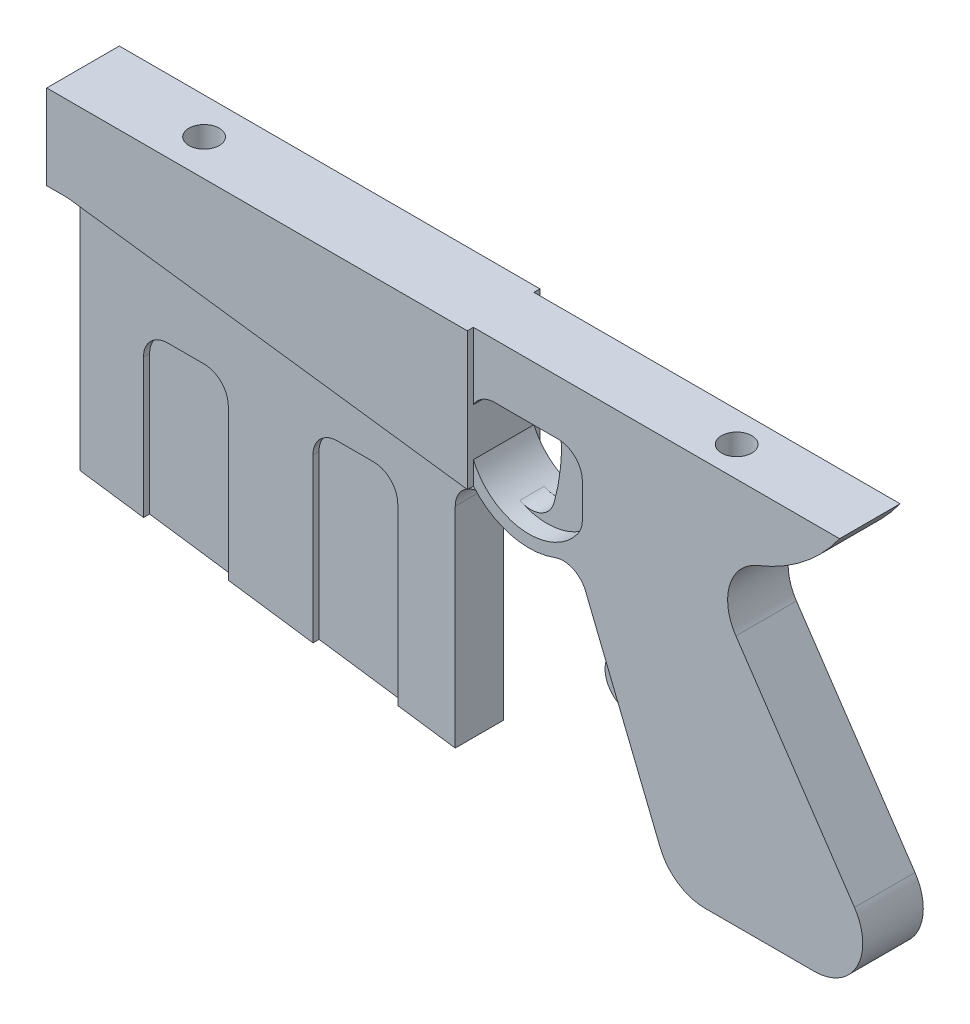
SolidWorks part; units mm, degrees
ref_plane "前视基准面" through (0, 0, 0) normal (0, 0, 1) x (1, 0, 0)
ref_plane "上视基准面" through (0, 0, 0) normal (0, 1, 0) x (1, 0, 0)
ref_plane "右视基准面" through (0, 0, 0) normal (1, 0, 0) x (0, 0, -1)
sketch "草图1" plane through (0, 0, 0) normal (0, 0, 1) x (1, 0, 0)
  line L0 (0, 0) -> (130, 0)
  line L1 (0, 0) -> (0, -14)
  line L2 (0, -14) -> (3.5, -14)
  line L3 (3.5, -14) -> (65.5, -22.7135)
  line L4 (65.5, -22.7135) -> (69.5, -22.7135)
  line L5 (88.0267, -28.48) -> (100.3562, -58.9969)
  line L6 (107.7737, -64) -> (125.8318, -64)
  line L7 (112.8677, -22.4735) -> (132.4641, -51.5265)
  line L8 (100.3562, -58.9969) -> (110.2182, -83.4061) construction
  line L9 (107.7737, -64) -> (101.1244, -64) construction
  line L10 (132.4641, -51.5265) -> (151.8382, -80.2497) construction
  line L11 (125.8318, -64) -> (183.2741, -64) construction
  line L13 (83.5, -9) -> (73, -9)
  line L14 (69, -13) -> (69, -17.4609)
  line L15 (3.5, -14) -> (3.5, -54)
  line L16 (3.5, -54) -> (65.5, -62.7135)
  line L17 (65.5, -62.7135) -> (65.5, -28.0957)
  line L18 (14, -55.4757) -> (14, -32.5)
  line L19 (18, -28.5) -> (24, -28.5)
  line L20 (28, -32.5) -> (28, -57.4433)
  line L21 (42, -59.4108) -> (42, -32.5)
  line L22 (46, -28.5) -> (52, -28.5)
  line L23 (56, -32.5) -> (56, -61.3784)
  line L24 (69.5, -22.7135) -> (69.5, 0)
  line L25 (87.5, -13) -> (87.5, -18.5899)
  arc A0 (116.5555, -10.5616) -> (130, 0) centre (105.5135, 17.3324) ccw
  arc A2 (69.5, -22.7135) -> (82.9116, -26.2338) centre (78.6925, -15) ccw
  arc A3 (100.3562, -58.9969) -> (107.7737, -64) centre (107.7737, -56) ccw
  arc A4 (125.8318, -64) -> (132.4641, -51.5265) centre (125.8318, -56) ccw
  arc A5 (116.5555, -10.5616) -> (112.8677, -22.4735) centre (119.5, -18) ccw
  arc A8 (69, -17.4609) -> (86.705, -20.9832) centre (78.6925, -15) ccw
  arc A9 (95.3649, -46.643) -> (92.5969, -44.2536) centre (91.6562, -48.1414) ccw
  arc A10 (88.0267, -28.48) -> (82.9116, -26.2338) centre (84.3179, -29.9785) ccw
  arc A11 (89.931, -37.6552) -> (90.2624, -34.0136) centre (86.5536, -35.512) ccw
  arc A13 (89.931, -37.6552) -> (92.5969, -44.2536) centre (93.6262, -40) ccw
  arc A14 (71.7981, -24.8218) -> (65.5, -28.0957) centre (69.5, -28.0957) ccw
  arc A15 (18, -28.5) -> (14, -32.5) centre (18, -32.5) ccw
  arc A16 (28, -32.5) -> (24, -28.5) centre (24, -32.5) ccw
  arc A17 (46, -28.5) -> (42, -32.5) centre (46, -32.5) ccw
  arc A18 (56, -32.5) -> (52, -28.5) centre (52, -32.5) ccw
  arc A20 (81.0852, -13.1161) -> (79.837, -21.4174) centre (46.1, -12.1) cw
  arc A26 (87.5, -13) -> (83.5, -9) centre (83.5, -13) ccw
  arc A27 (73, -9) -> (69, -13) centre (73, -13) ccw
  arc A29 (86.705, -20.9832) -> (87.5, -18.5899) centre (83.5, -18.5899) ccw
  arc A30 (81.0852, -13.1161) -> (77.0869, -9) centre (77.0869, -13) ccw
  arc A31 (74.1739, -23.9209) -> (79.837, -21.4174) centre (75.9814, -20.3526) ccw
  point P25 (102.3776, -64)
  point P26 (140.8776, -64)
  point P32 (86.5536, -21.4174)
  point P66 (81.0869, -13)
  point P72 (79.7986, -21.5479)
  point P73 (85.4484, -22.7135)
  point P75 (87.5, -23.1424)
  point P77 (87.5, -19.7475)
  dimension "D1" = 8
  dimension "D6" = 12
  dimension "D7" = 15
  dimension "D10" = 8
  dimension "D11" = 56
  dimension "D15" = 8
  dimension "D18" = 60
  dimension "D20" = 10
  dimension "D23" = 4
  dimension "D24" = 28.5
  dimension "D25" = 4
  dimension "D26" = 40
  dimension "D27" = 3.5
  dimension "D28" = 40
  dimension "D30" = 4
  dimension "D31" = 4
  dimension "D32" = 10.5
  dimension "D36" = 12.1
  dimension "D38" = 35
  dimension "D39" = 4
  dimension "D21" = 87.5
  dimension "D22" = 18.5
  dimension "D2" = 3.5
  dimension "D3" = 14
  dimension "D4" = 62
  dimension "D5" = 4
  dimension "D8" = 78.6925
  dimension "D9" = 130
  dimension "D12" = 112
  dimension "D13" = 38.5
  dimension "D14" = 64
  dimension "D16" = 10.5
  dimension "D17" = 18
  dimension "D19" = 9
  dimension "D29" = 82
  dimension "D33" = 14
  dimension "D34" = 14
  dimension "D35" = 14
  dimension "D37" = 46.1
extrude "凸台-拉伸8" add sketch "草图1" along normal blind 4 and the other way blind 4 contours A27 L24 L0 L1 L2 L3 L4 A8 L14 | A18 L23 L16 L17 A14 A2 L4 L3 L15 L18 A15 L19 A16 L20 L21 A17 L22 region at (37.6933, -9.3888, 0) region at (33.9493, -35.5921, 0)
extrude "凸台-拉伸9" add sketch "草图1<10>" along normal blind 5 and the other way blind 5 contours A27 L13 A26 A8 L24 A2 A10 L5 A3 L6 A4 L7 A5 A0 L0 region at (105.0804, -29.813, 0)
sketch "草图1<10>" plane through (0, 0, 0) normal (0, 0, 1) x (1, 0, 0) same geometry as "草图1"
extrude "凸台-拉伸10" add sketch "草图1<11>" along normal blind 2 and the other way blind 2 contours A8 A26 L13 A20 region at (83.3294, -16.8603, 0)
sketch "草图1<11>" plane through (0, 0, 0) normal (0, 0, 1) x (1, 0, 0) same geometry as "草图1"
extrude "凸台-拉伸11" add sketch "草图1<12>" along normal blind 3 and the other way blind 3 contours A11 A13 A9 L5 region at (91.5323, -40.846, 0)
sketch "草图1<12>" plane through (0, 0, 0) normal (0, 0, 1) x (1, 0, 0) same geometry as "草图1"
extrude "凸台-拉伸12" add sketch "草图1<13>" along normal blind 3 and the other way blind 3 contours L20 A16 L19 A15 L18 L16 | L23 A18 L22 A17 L21 L16 region at (21.0836, -42.7193, 0) region at (49.0731, -44.6876, 0)
sketch "草图1<13>" plane through (0, 0, 0) normal (0, 0, 1) x (1, 0, 0) same geometry as "草图1"
sketch "草图13" plane through (0, 0, 0) normal (0, 0, 1) x (1, 0, 0)
  line L0 (69.5, 0) -> (69.5, -22.7135)
  line L1 (69.5, -11.0635) -> (69.5, 0) construction
  line L2 (69.5, -11.0635) -> (69.5, 0) construction
  line L3 (69.5, -22.7135) -> (3.5, -14)
  line L4 (3.5, -14) -> (0, -14)
  line L5 (0, -14) -> (0, 0)
  line L6 (0, 0) -> (69.5, 0)
extrude "凸台-拉伸13" add sketch "草图13" along normal blind 6 and the other way blind 6
hole_wizard "M6 螺纹孔2" positions "草图11" profile "草图12" tap size "M6" standard "GB"
sketch "草图11" plane through (0, 0, 0) normal (0, 1, 0) x (1, 0, 0)
  point P0 (20, 0)
  point P2 (108, 0)
  dimension "D1" = 20
  dimension "D2" = 88
sketch "草图12" plane through (20, 0, 0) normal (1, 0, 0) x (0, 0, 1)
  line L0 (0, 0) -> (0, 16.5022)
  line L1 (0, 16.5022) -> (2.5, 15)
  line L2 (2.5, 15) -> (2.5, 0)
  line L5 (2.5, 0) -> (0, 0)
  line L10 (0, 16.5022) -> (-2.5, 15) construction
  line L11 (0, -6.35) -> (0, 107.95) construction
  dimension "螺纹孔钻头直径" = 5
  dimension "螺纹孔钻头深度" = 15
  dimension "导头角度" = 118
cosmetic thread "孔螺蚊线2" parameters "D1"=12, "D2"=6
cosmetic thread "孔螺蚊线3" parameters "D1"=12, "D2"=6
